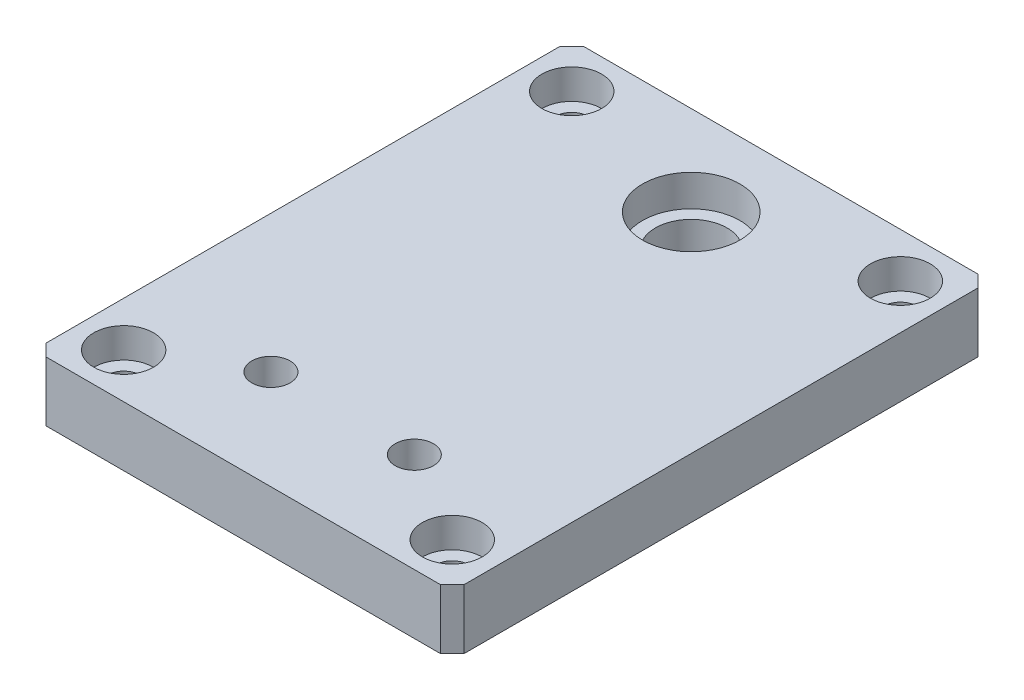
SolidWorks part; units mm, degrees
ref_plane "Front Plane" through (0, 0, 0) normal (0, 0, 1) x (1, 0, 0)
ref_plane "Top Plane" through (0, 0, 0) normal (0, 1, 0) x (1, 0, 0)
ref_plane "Right Plane" through (0, 0, 0) normal (1, 0, 0) x (0, 0, -1)
sketch "Sketch1" plane through (0, 0, 0) normal (0, 1, 0) x (1, 0, 0)
  line L1 (-35, -45) -> (35, -45)
  line L2 (-35, -45) -> (-35, 45)
  line L3 (-35, 45) -> (35, 45)
  line L4 (35, -45) -> (35, 45)
  line L5 (-35, -45) -> (35, 45) construction
  line L6 (-35, 45) -> (35, -45) construction
  point P0 (0, 0)
  dimension "D1" = 70
  dimension "D2" = 90
extrude "Boss-Extrude1" add sketch "Sketch1" along normal blind 10
sketch "Sketch4" plane through (0, 10, 0) normal (0, 1, 0) x (1, 0, 0)
  line L0 (-35, 45) -> (-35, -45) construction
  line L1 (35, 45) -> (-35, 45) construction
  line L3 (35, -45) -> (35, 45) construction
  line L4 (-35, -45) -> (35, -45) construction
  point P0 (-27.5, -37.5)
  point P2 (-27.5, 37.5)
  point P4 (27.5, 37.5)
  point P6 (27.5, -37.5)
  dimension "D1" = 7.5
  dimension "D2" = 7.5
  dimension "D3" = 7.5
  dimension "D4" = 7.5
hole_wizard "CBORE for M5 SHCS1" positions "Sketch4" profile "Sketch3" counterbore size "M5" standard "ANSI Metric" end condition through all
sketch "Sketch3" plane through (-27.5, 10, 37.5) normal (1, 0, 0) x (0, 0, 1)
  line L0 (0, 0) -> (0, 10)
  line L1 (0, 10) -> (2.75, 10)
  line L3 (2.75, 10) -> (2.75, 5)
  line L4 (2.75, 5) -> (5, 5)
  line L5 (5, 5) -> (5, 0)
  line L7 (5, 0) -> (0, 0)
  line L11 (0, -6.35) -> (0, 107.95) construction
  dimension "Thru Hole Dia." = 5.5
  dimension "Thru Hole Depth" = 10
  dimension "C'Bore Dia." = 10
  dimension "C'Bore Depth" = 5
sketch "Sketch7" plane through (0, 10, 0) normal (0, 1, 0) x (1, 0, 0)
  line L0 (35, 45) -> (-35, 45) construction
  point P0 (0, 30)
  dimension "D1" = 15
hole_wizard "Ø1.0mm Dowel Hole1" positions "Sketch7" profile "Sketch6" hole size "Ø1.0" standard "ANSI Metric"
sketch "Sketch6" plane through (0, 10, -30) normal (1, 0, 0) x (0, 0, 1)
  line L0 (0, 0) -> (0, 5.3)
  line L1 (0, 5.3) -> (8.15, 5.3)
  line L2 (8.15, 5.3) -> (8.15, 0)
  line L5 (8.15, 0) -> (0, 0)
  line L10 (0, 5.3) -> (-8.15, 5.3) construction
  line L11 (0, -6.35) -> (0, 107.95) construction
  dimension "Hole Dia." = 16.3
  dimension "Hole Depth" = 5.3
  dimension "Drill Angle" = 180
sketch "Sketch13" plane through (0, 4.7, 0) normal (0, 1, 0) x (1, 0, 0)
  point P0 (0, 30)
hole_wizard "Ø1.0mm Dowel Hole3" positions "Sketch13" profile "Sketch12" hole size "Ø1.0" standard "ANSI Metric" end condition through all
sketch "Sketch12" plane through (0, 4.7, -30) normal (1, 0, 0) x (0, 0, 1)
  line L0 (0, 0) -> (0, 4.7)
  line L1 (0, 4.7) -> (6, 4.7)
  line L2 (6, 4.7) -> (6, 0)
  line L5 (6, 0) -> (0, 0)
  line L11 (0, -6.35) -> (0, 107.95) construction
  dimension "Thru Hole Dia." = 12
  dimension "Thru Hole Depth" = 4.7
sketch "Sketch14" plane through (0, 10, 0) normal (0, 1, 0) x (1, 0, 0)
  circle A2 centre (12, -28.35) radius 3.2
  circle A3 centre (-12, -28.35) radius 3.2
  dimension "D5" = 6.4
  dimension "D6" = 6.4
  dimension "D1" = 28.35
  dimension "D2" = 12
  dimension "D3" = 12
  dimension "D4" = 28.35
extrude "Cut-Extrude1" cut sketch "Sketch14" against normal through all
chamfer "Chamfer1" distance 2 angle 45 4 edges at (35, 5, 45) (35, 5, -45) (-35, 5, -45) (-35, 5, 45)
equation "\"D1@Sketch4\" = 5 * 1.5"
equation "\"D2@Sketch4\" = \"D1@Sketch4\""
equation "\"D4@Sketch14\"=\"D1@Sketch14\""
